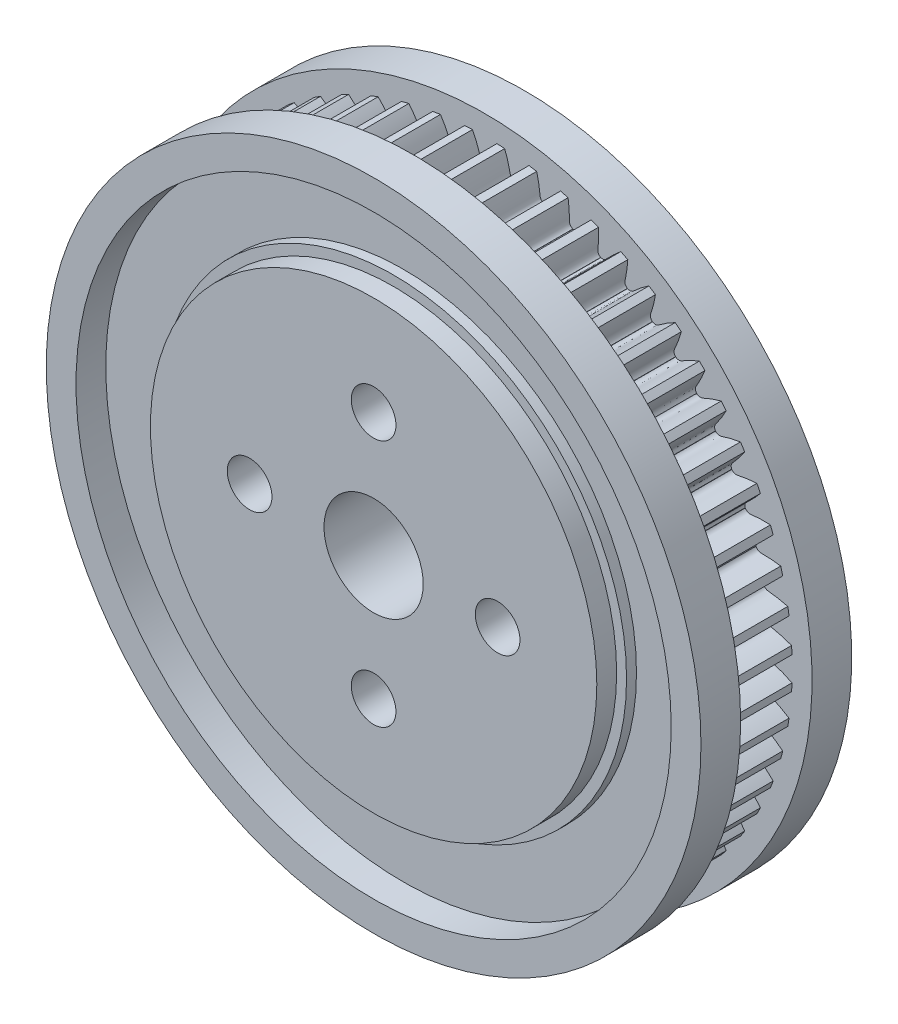
SolidWorks part; units mm, degrees
ref_plane "前视基准面" through (0, 0, 0) normal (0, 0, 1) x (1, 0, 0)
ref_plane "上视基准面" through (0, 0, 0) normal (0, 1, 0) x (1, 0, 0)
ref_plane "右视基准面" through (0, 0, 0) normal (1, 0, 0) x (0, 0, -1)
sketch "草图1" plane through (0, 0, 0) normal (0, 0, 1) x (1, 0, 0)
  circle A0 centre (0, 0) radius 31
extrude "凸台-拉伸1" add sketch "草图1" along normal blind 7.2
ref_axis "基准轴1" [suppressed] through (0, 0, -0.35) along (0, 0, 1)
sketch "草图2" plane through (0, 0, 0) normal (0, 0, 1) x (1, 0, 0)
  line L0 (0, 0) -> (0, 31) construction
  circle A0 centre (0, 0) radius 31 construction
  arc A1 (0.01, 28.75) -> (-0.01, 28.75) centre (0, 0) ccw
  arc A2 (4.2086, 35.0652) -> (-4.2086, 35.0652) centre (0, 0) ccw
  spline S0 degree 3 poles (0.01, 28.75) (0.4295, 28.8193) (0.4958, 29.1655) (0.6239, 29.5502) (0.684, 29.7232) (0.7519, 29.9052) (0.8274, 30.0965) (0.9111, 30.2965) (1.0033, 30.5052) (1.1044, 30.7222) (1.2149, 30.9473) (1.3349, 31.1801) (1.465, 31.4204) (1.6054, 31.6679) (1.7565, 31.9222) (1.9186, 32.183) (2.092, 32.45) (2.2771, 32.7228) (2.4741, 33.001) (2.6833, 33.2844) (2.905, 33.5724) (3.1395, 33.8647) (3.387, 34.1609) (3.7397, 34.5662) (4.0171, 34.8662) (4.2086, 35.0652) knots 0 0 0 0 0.112555 0.13496 0.158835 0.184181 0.210998 0.239286 0.269045 0.300275 0.332976 0.367147 0.40279 0.439904 0.478488 0.518544 0.56007 0.603067 0.647536 0.693475 0.740885 0.789766 0.840118 0.891941 1 1 1 1
  spline S1 degree 3 poles (-0.01, 28.75) (-0.4295, 28.8193) (-0.4958, 29.1655) (-0.6239, 29.5502) (-0.684, 29.7232) (-0.7519, 29.9052) (-0.8274, 30.0965) (-0.9111, 30.2965) (-1.0033, 30.5052) (-1.1044, 30.7222) (-1.2149, 30.9473) (-1.3349, 31.1801) (-1.465, 31.4204) (-1.6054, 31.6679) (-1.7565, 31.9222) (-1.9186, 32.183) (-2.092, 32.45) (-2.2771, 32.7228) (-2.4741, 33.001) (-2.6833, 33.2844) (-2.905, 33.5724) (-3.1395, 33.8647) (-3.387, 34.1609) (-3.7397, 34.5662) (-4.0171, 34.8662) (-4.2086, 35.0652) knots 0 0 0 0 0.112555 0.13496 0.158835 0.184181 0.210998 0.239286 0.269045 0.300275 0.332976 0.367147 0.40279 0.439904 0.478488 0.518544 0.56007 0.603067 0.647536 0.693475 0.740885 0.789766 0.840118 0.891941 1 1 1 1
extrude "切除-拉伸1" cut sketch "草图2" along normal through all
pattern_circular "阵列(圆周)1" count 60 every 6 about axis through (0, 0, -0.35) along (0, 0, 1) of "切除-拉伸1"
sketch "草图3" plane through (0, 0, 0) normal (0, 0, 1) x (1, 0, 0)
  circle A0 centre (0, 0) radius 30 construction
  dimension "Dn" = 60
sketch "草图4" plane through (0, 0, 7.2) normal (0, 0, 1) x (1, 0, 0)
  circle A0 centre (0, 0) radius 33
  dimension "D1" = 66
extrude "凸台-拉伸2" add sketch "草图4" along normal blind 4
sketch "草图5" plane through (0, 0, 11.2) normal (0, 0, 1) x (1, 0, 0)
  circle A0 centre (0, 0) radius 22.5
  circle A1 centre (0, 0) radius 30
  dimension "D1" = 45
  dimension "D2" = 60
extrude "切除-拉伸2" cut sketch "草图5" against normal blind 3
sketch "a" plane through (0, 0, 8.2) normal (0, 0, 1) x (1, 0, 0)
  circle A0 centre (0, 0) radius 22.5
  circle A1 centre (0, 0) radius 23.5
  dimension "D1" = 45
  dimension "D2" = 47
extrude "凸台-拉伸3" add sketch "a" along normal blind 1
sketch "草图8" plane through (0, 0, 0) normal (0, 0, -1) x (-1, 0, 0)
  circle A0 centre (0, 0) radius 33
  dimension "D1" = 66
extrude "凸台-拉伸4" add sketch "草图8" along normal blind 4
sketch "草图9" plane through (0, 0, -4) normal (0, 0, -1) x (-1, 0, 0)
  circle A0 centre (0, 0) radius 30
  dimension "D1" = 60
extrude "切除-拉伸3" cut sketch "草图9" against normal blind 2
sketch "草图10" plane through (0, 0, 11.2) normal (0, 0, 1) x (1, 0, 0)
  circle A0 centre (0, 0) radius 5
  circle A1 centre (0, 12.5) radius 1.6
  circle A2 centre (0, 0) radius 12.5 construction
  circle A3 centre (12.5, 0) radius 1.6
  circle A4 centre (0, -12.5) radius 1.6
  circle A5 centre (-12.5, 0) radius 1.6
  point P15 (0, 0)
  dimension "D1" = 10
  dimension "D2" = 3.2
  dimension "D3" = 25
  dimension "D4" = 4
extrude "切除-拉伸4" cut sketch "草图10" against normal through all
sketch "草图11" plane through (0, 0, 11.2) normal (0, 0, 1) x (1, 0, 0)
  circle A0 centre (0, 12.5) radius 2.25
  circle A1 centre (12.5, 0) radius 2.25
  circle A2 centre (0, -12.5) radius 2.25
  circle A3 centre (-12.5, 0) radius 2.25
  point P12 (0, 0)
  dimension "D1" = 4.5
  dimension "D2" = 4
extrude "切除-拉伸5" cut sketch "草图11" against normal blind 4
